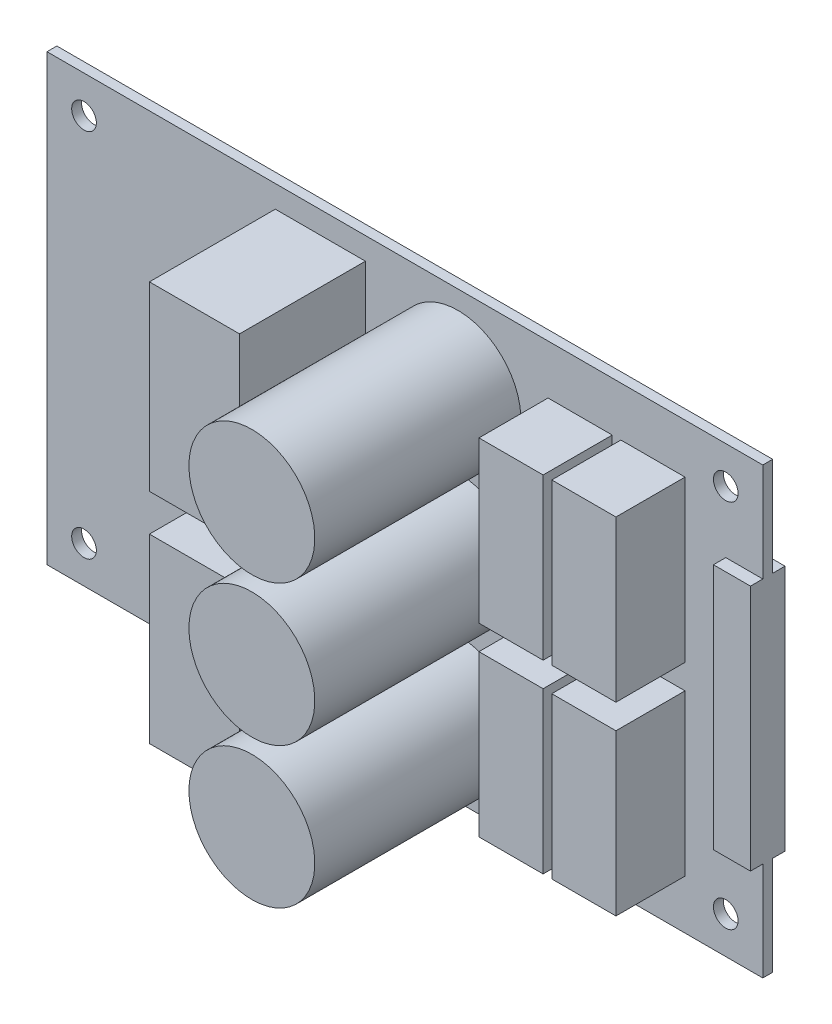
SolidWorks part; units mm, degrees
ref_plane "前视基准面" through (0, 0, 0) normal (0, 0, 1) x (1, 0, 0)
ref_plane "上视基准面" through (0, 0, 0) normal (0, 1, 0) x (1, 0, 0)
ref_plane "右视基准面" through (0, 0, 0) normal (1, 0, 0) x (0, 0, -1)
other "Configuration Table"
sketch "草图1" plane through (0, 0, 0) normal (0, 0, 1) x (1, 0, 0)
  line L6 (-29, -18) -> (29, -18)
  line L11 (-29, -18) -> (-29, 18)
  line L12 (-29, 18) -> (29, 18)
  line L13 (29, -18) -> (29, 18)
  line L14 (-29, -18) -> (29, 18) construction
  line L15 (-29, 18) -> (29, -18) construction
  circle A0 centre (-26, -15) radius 1
  circle A1 centre (-26, 15) radius 1
  circle A2 centre (26, 15) radius 1
  circle A3 centre (26, -15) radius 1
  point P0 (0, 0)
  point P13 (26, -11.5289)
  point P14 (0, 0)
  point P15 (0, 0)
  point P16 (0, 0)
  point P17 (0, 0)
  point P18 (0, 0)
  point P19 (15.9878, 11.1004)
  point P20 (0, 0)
  point P21 (0, 0)
  point P22 (0, 0)
  dimension "D1" = 36
  dimension "D2" = 58
  dimension "D4" = 15
  dimension "D5" = 3
  dimension "D6" = 3
  dimension "D3" = 2
  dimension "D7" = 15
extrude "凸台-拉伸1" add sketch "草图1" along normal blind 0.8 contours L12 | A2 | L12 L13 L6 L11 | A1 | A3 | A0 region at (26, 15, 0)
sketch "草图2" plane through (0, 0, 0) normal (0, 0, -1) x (-1, 0, 0)
  line L0 (29, 18) -> (-29, 18) construction
  line L1 (-21, -14) -> (-19.2, -14)
  line L2 (-21, -14) -> (-21, -12.2)
  line L3 (-21, -12.2) -> (-19.2, -12.2)
  line L4 (-19.2, -14) -> (-19.2, -12.2)
  line L5 (-21, -1) -> (-19.2, -1)
  line L6 (-21, -1) -> (-21, -2.8)
  line L7 (-21, -2.8) -> (-19.2, -2.8)
  line L8 (-19.2, -1) -> (-19.2, -2.8)
  line L9 (-21, 2.8) -> (-19.2, 2.8)
  line L10 (-21, 2.8) -> (-21, 1)
  line L11 (-21, 1) -> (-19.2, 1)
  line L12 (-19.2, 2.8) -> (-19.2, 1)
  line L13 (-21, 14) -> (-19.2, 14)
  line L14 (-21, 14) -> (-21, 12.2)
  line L15 (-21, 12.2) -> (-19.2, 12.2)
  line L16 (-19.2, 14) -> (-19.2, 12.2)
  line L17 (-15.1, 14) -> (-13.3, 14)
  line L18 (-15.1, 14) -> (-15.1, 12.2)
  line L19 (-15.1, 12.2) -> (-13.3, 12.2)
  line L20 (-13.3, 14) -> (-13.3, 12.2)
  line L21 (-15.1, 2.8) -> (-13.3, 2.8)
  line L22 (-15.1, 2.8) -> (-15.1, 1)
  line L23 (-15.1, 1) -> (-13.3, 1)
  line L24 (-13.3, 2.8) -> (-13.3, 1)
  line L25 (-15.1, -1) -> (-13.3, -1)
  line L26 (-15.1, -1) -> (-15.1, -2.8)
  line L27 (-15.1, -2.8) -> (-13.3, -2.8)
  line L28 (-13.3, -1) -> (-13.3, -2.8)
  line L29 (-15.1, -12.2) -> (-13.3, -12.2)
  line L30 (-15.1, -12.2) -> (-15.1, -14)
  line L31 (-15.1, -14) -> (-13.3, -14)
  line L32 (-13.3, -12.2) -> (-13.3, -14)
  line L33 (29, -18) -> (-29, -18) construction
  line L34 (-29, -18) -> (-29, 18) construction
  line L35 (29, -18) -> (29, 18) construction
  line L37 (-22.7, 14) -> (-17.5, 14)
  line L38 (-22.7, 14) -> (-22.7, 1)
  line L39 (-22.7, 1) -> (-17.5, 1)
  line L40 (-17.5, 14) -> (-17.5, 1)
  line L41 (-16.8, 14) -> (-11.6, 14)
  line L42 (-16.8, 14) -> (-16.8, 1)
  line L43 (-16.8, 1) -> (-11.6, 1)
  line L44 (-11.6, 14) -> (-11.6, 1)
  line L45 (-22.7, -1) -> (-17.5, -1)
  line L46 (-22.7, -1) -> (-22.7, -14)
  line L47 (-22.7, -14) -> (-17.5, -14)
  line L48 (-17.5, -1) -> (-17.5, -14)
  line L49 (-16.8, -1) -> (-11.6, -1)
  line L50 (-16.8, -1) -> (-16.8, -14)
  line L51 (-16.8, -14) -> (-11.6, -14)
  line L52 (-11.6, -1) -> (-11.6, -14)
  point P56 (0, 0)
  point P57 (-20.1, 14)
  point P59 (-14.2, 14)
  dimension "D1" = 32
  dimension "D2" = 32
  dimension "D3" = 9.8
  dimension "D4" = 50
  dimension "D5" = 15.7
  dimension "D6" = 17
  dimension "D7" = 17
  dimension "D8" = 5.2
extrude "凸台-拉伸2" add sketch "草图2" along normal blind 1 contours L30 L31 L32 L29 | L26 L27 L28 L25 | L24 L23 L22 L21 | L20 L19 L18 L17 | L15 L16 L13 L14 | L10 L11 L12 L9 | L7 L8 L5 L6 | L2 L3 L4 L1
extrude "凸台-拉伸3" add sketch "草图2<3>" against normal blind 5.6 from surface contours L50 L51 L52 L49 | L48 L47 L46 L45 | L42 L43 L44 L41 | L40 L39 L38 L37 starting at face at (0, 0, 0.8)
sketch "草图2<3>" plane through (0, 0, 0) normal (0, 0, -1) x (-1, 0, 0) same geometry as "草图2"
sketch "草图3" plane through (0, 0, 0) normal (0, 0, -1) x (-1, 0, 0)
  line L0 (29, 18) -> (-29, 18) construction
  line L1 (9, 13.2) -> (10.5, 13.2)
  line L2 (9, 13.2) -> (9, 4.5)
  line L3 (9, 4.5) -> (10.5, 4.5)
  line L4 (10.5, 13.2) -> (10.5, 4.5)
  line L5 (9, -4.5) -> (10.5, -4.5)
  line L6 (9, -4.5) -> (9, -13.2)
  line L7 (9, -13.2) -> (10.5, -13.2)
  line L8 (10.5, -4.5) -> (10.5, -13.2)
  line L9 (29, -18) -> (-29, -18) construction
  line L10 (29, -18) -> (29, 18) construction
  line L11 (-29, -18) -> (-29, 18) construction
  line L12 (9, 13.2) -> (9, 16.2) construction
  line L13 (10.5, 16.2) -> (3.2, 16.2)
  line L14 (10.5, 16.2) -> (10.5, 1.5)
  line L15 (10.5, 1.5) -> (3.2, 1.5)
  line L16 (3.2, 16.2) -> (3.2, 1.5)
  line L17 (10.5, -1.5) -> (3.2, -1.5)
  line L18 (10.5, -1.5) -> (10.5, -16.2)
  line L19 (10.5, -16.2) -> (3.2, -16.2)
  line L20 (3.2, -1.5) -> (3.2, -16.2)
  line L21 (9, 4.5) -> (9, 1.5) construction
  dimension "D1" = 13.5
  dimension "D2" = 13.5
  dimension "D3" = 31.2
  dimension "D4" = 20
  dimension "D5" = 39.5
  dimension "D6" = 25.8
  dimension "D7" = 34.2
  dimension "D8" = 34.2
extrude "凸台-拉伸4" add sketch "草图3" along normal blind 1 contours L4 L3 L2 L1 | L8 L7 L6 L5
extrude "凸台-拉伸5" add sketch "草图3<3>" against normal blind 10.2 from surface contours L15 L16 L13 L14 | L19 L20 L17 L18 starting at face at (20.1, 7.5, 0.8)
sketch "草图3<3>" plane through (0, 0, 0) normal (0, 0, -1) x (-1, 0, 0) same geometry as "草图3"
sketch "草图4" plane through (0, 0, 0) normal (0, 0, -1) x (-1, 0, 0)
  line L0 (29, -18) -> (-29, -18) construction
  line L1 (-6.8, 1) -> (-4.8, 1)
  line L2 (-6.8, 1) -> (-6.8, -1)
  line L3 (-6.8, -1) -> (-4.8, -1)
  line L4 (-4.8, 1) -> (-4.8, -1)
  line L5 (-3.8, 1) -> (-1.8, 1)
  line L6 (-3.8, 1) -> (-3.8, -1)
  line L7 (-3.8, -1) -> (-1.8, -1)
  line L8 (-1.8, 1) -> (-1.8, -1)
  line L9 (-6.8, 12.4) -> (-4.8, 12.4)
  line L10 (-6.8, 12.4) -> (-6.8, 10.4)
  line L11 (-6.8, 10.4) -> (-4.8, 10.4)
  line L12 (-4.8, 12.4) -> (-4.8, 10.4)
  line L13 (-3.8, 12.4) -> (-1.8, 12.4)
  line L14 (-3.8, 12.4) -> (-3.8, 10.4)
  line L15 (-3.8, 10.4) -> (-1.8, 10.4)
  line L16 (-1.8, 12.4) -> (-1.8, 10.4)
  line L17 (-6.8, -10.4) -> (-4.8, -10.4)
  line L18 (-6.8, -10.4) -> (-6.8, -12.4)
  line L19 (-6.8, -12.4) -> (-4.8, -12.4)
  line L20 (-4.8, -10.4) -> (-4.8, -12.4)
  line L21 (-3.8, -10.4) -> (-1.8, -10.4)
  line L22 (-3.8, -10.4) -> (-3.8, -12.4)
  line L23 (-3.8, -12.4) -> (-1.8, -12.4)
  line L24 (-1.8, -10.4) -> (-1.8, -12.4)
  line L25 (29, 18) -> (-29, 18) construction
  line L26 (29, -18) -> (29, 18) construction
  line L27 (-29, -18) -> (-29, 18) construction
  line L28 (-4.8, 0) -> (-4.3, 0) construction
  line L29 (-4.3, 0) -> (-3.8, 0) construction
  line L30 (-4.8, 11.4) -> (-4.3, 11.4) construction
  line L31 (-4.3, 11.4) -> (-3.8, 11.4) construction
  line L32 (-4.8, -11.4) -> (-4.3, -11.4) construction
  line L33 (-4.3, -11.4) -> (-3.8, -11.4) construction
  circle A0 centre (-4.3, 0) radius 5.1
  circle A1 centre (-4.3, 11.4) radius 5.1
  circle A2 centre (-4.3, -11.4) radius 5.1
  dimension "D7" = 10.2
  dimension "D1" = 19
  dimension "D2" = 19
  dimension "D3" = 35.8
  dimension "D4" = 27.2
  dimension "D5" = 7.6
  dimension "D6" = 7.6
extrude "凸台-拉伸6" add sketch "草图4" along normal blind 1 contours L19 L20 L17 L18 | L23 L24 L21 L22 | L3 L4 L1 L2 | L7 L8 L5 L6 | L11 L12 L9 L10 | L15 L16 L13 L14
extrude "凸台-拉伸7" add sketch "草图4<3>" against normal blind 16.7 from surface contours A1 | A0 | A2 starting at face at (-6.85, -8.85, 0.8)
sketch "草图4<3>" plane through (0, 0, 0) normal (0, 0, -1) x (-1, 0, 0) same geometry as "草图4"
sketch "草图5" plane through (0, 0, 0) normal (0, 0, -1) x (-1, 0, 0)
  line L0 (-29, -18) -> (-29, 18) construction
  line L1 (-29, 10) -> (-26, 10)
  line L2 (-29, 10) -> (-29, -10)
  line L3 (-29, -10) -> (-26, -10)
  line L4 (-26, 10) -> (-26, -10)
  point P6 (-29, 0)
  point P7 (0, 0)
  dimension "D1" = 20
  dimension "D2" = 3
extrude "凸台-拉伸8" add sketch "草图5" along normal blind 1
extrude "凸台-拉伸9" add sketch "草图5<2>" against normal blind 1 from surface starting at face at (-0.8, -11.4, 0.8)
sketch "草图5<2>" plane through (0, 0, 0) normal (0, 0, -1) x (-1, 0, 0) same geometry as "草图5"
